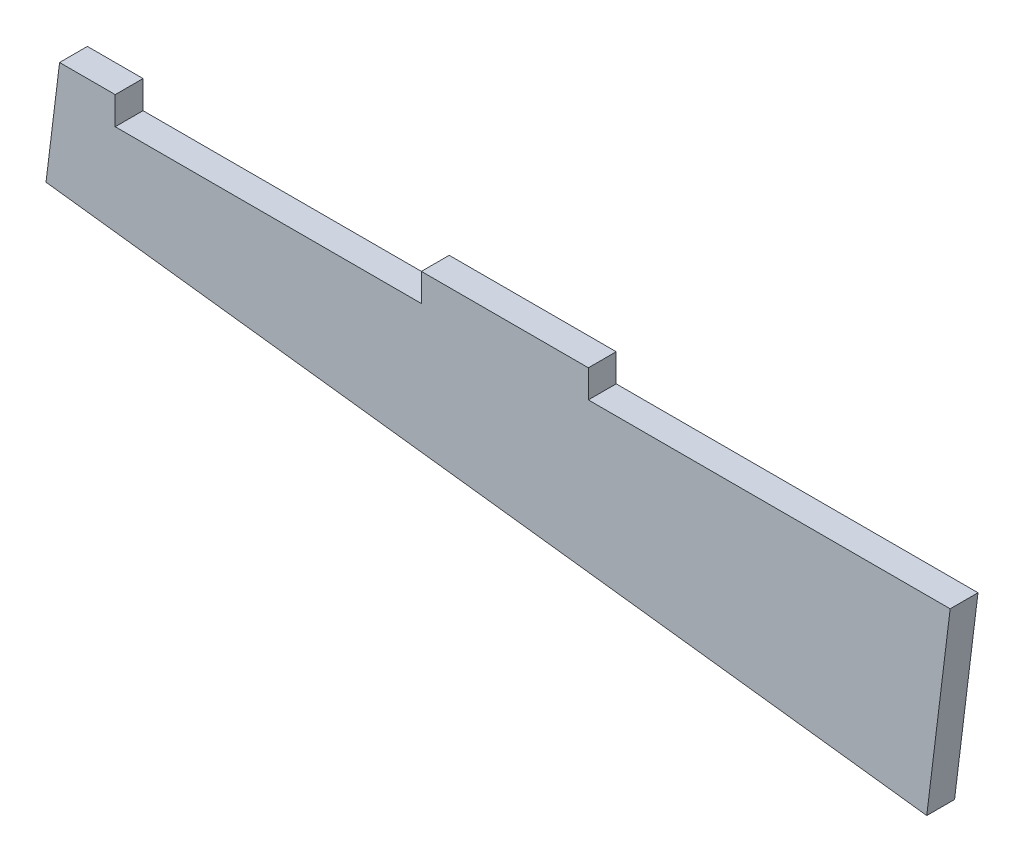
SolidWorks part; units mm, degrees
ref_plane "Front Plane" through (0, 0, 0) normal (0, 0, 1) x (1, 0, 0)
ref_plane "Top Plane" through (0, 0, 0) normal (0, 1, 0) x (1, 0, 0)
ref_plane "Right Plane" through (0, 0, 0) normal (1, 0, 0) x (0, 0, -1)
sketch "Sketch1" plane through (0, 0, 0) normal (0, 0, 1) x (1, 0, 0)
  line L0 (-195.3168, -62.6592) -> (-182.6168, -62.6592)
  line L4 (-182.6168, -62.6592) -> (-182.6168, -69.0092)
  line L5 (-182.6168, -69.0092) -> (-112.7668, -69.0092)
  line L6 (-112.7668, -69.0092) -> (-112.7668, -62.6592)
  line L7 (-112.7668, -62.6592) -> (-74.6668, -62.6592)
  line L8 (-74.6668, -62.6592) -> (-74.6668, -69.0092)
  line L9 (-74.6668, -69.0092) -> (7.8832, -69.0092)
  line L10 (7.8832, -69.0092) -> (2.5379, -112.5435)
  line L11 (2.5379, -112.5435) -> (-198.4122, -87.8699)
  line L12 (-198.4122, -87.8699) -> (-195.3168, -62.6592)
  line L13 (-361.6766, -49.634) -> (32.0234, -97.9743) construction
  point P2 (-62.7286, -30.0583)
  dimension "D1" = 12.7
  dimension "D2" = 6.35
  dimension "D3" = 69.85
  dimension "D4" = 38.1
  dimension "D5" = 82.55
  dimension "D6" = 25.4
extrude "Boss-Extrude1" add sketch "Sketch1" against normal blind 6.35
